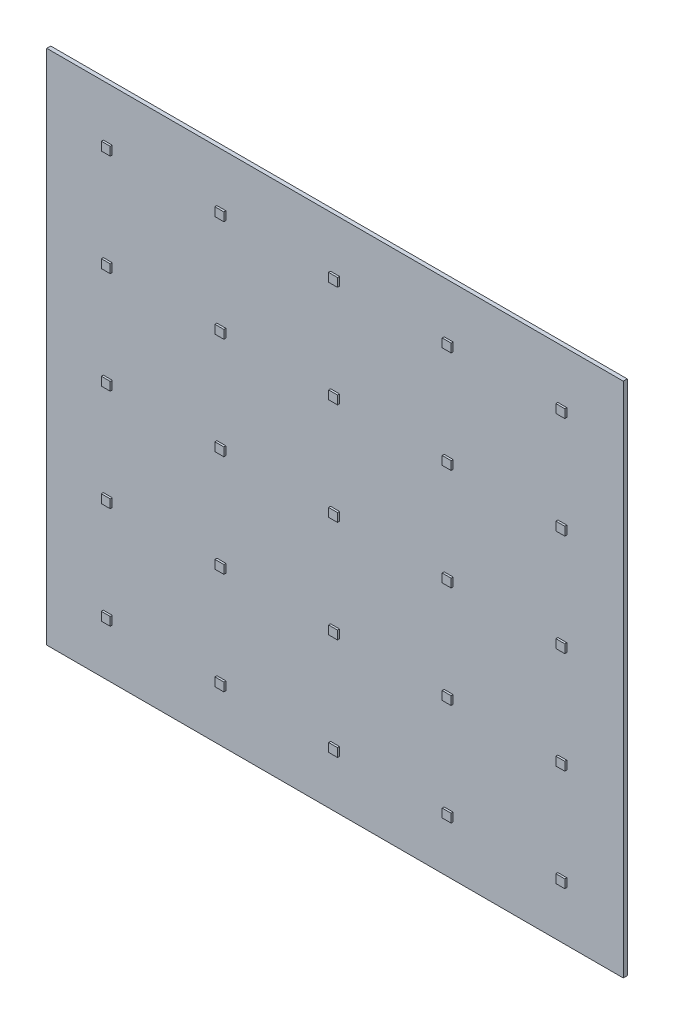
SolidWorks part; units mm, degrees
ref_plane "前视基准面" through (0, 0, 0) normal (0, 0, 1) x (1, 0, 0)
ref_plane "上视基准面" through (0, 0, 0) normal (0, 1, 0) x (1, 0, 0)
ref_plane "右视基准面" through (0, 0, 0) normal (1, 0, 0) x (0, 0, -1)
sketch "草图1" plane through (0, 0, 0) normal (0, 0, 1) x (1, 0, 0)
  line L1 (-72.5, -65) -> (72.5, -65)
  line L2 (-72.5, -65) -> (-72.5, 65)
  line L3 (-72.5, 65) -> (72.5, 65)
  line L4 (72.5, -65) -> (72.5, 65)
  line L5 (-72.5, -65) -> (72.5, 65) construction
  line L6 (-72.5, 65) -> (72.5, -65) construction
  point P0 (0, 0)
  dimension "D1" = 130
  dimension "D2" = 145
extrude "凸台-拉伸1" add sketch "草图1" along normal blind 1
sketch "草图2" plane through (0, 0, 1) normal (0, 0, 1) x (1, 0, 0)
  line L0 (-29.705, 49.9885) -> (-29.705, 52.1385)
  line L1 (-58.285, 49.9885) -> (-56.035, 49.9885)
  line L2 (-58.285, 49.9885) -> (-58.285, 52.1385)
  line L3 (-58.285, 52.1385) -> (-56.035, 52.1385)
  line L4 (-56.035, 49.9885) -> (-56.035, 52.1385)
  line L5 (-58.285, 49.9885) -> (-56.035, 52.1385) construction
  line L6 (-58.285, 52.1385) -> (-56.035, 49.9885) construction
  line L7 (-29.705, 49.9885) -> (-27.455, 49.9885)
  line L8 (-27.455, 49.9885) -> (-27.455, 52.1385)
  line L9 (-29.705, 52.1385) -> (-27.455, 52.1385)
  line L10 (-29.705, 49.9885) -> (-27.455, 52.1385) construction
  line L11 (-29.705, 52.1385) -> (-27.455, 49.9885) construction
  line L12 (-1.125, 49.9885) -> (-1.125, 52.1385)
  line L13 (-1.125, 49.9885) -> (1.125, 49.9885)
  line L14 (1.125, 49.9885) -> (1.125, 52.1385)
  line L15 (-1.125, 52.1385) -> (1.125, 52.1385)
  line L16 (-1.125, 49.9885) -> (1.125, 52.1385) construction
  line L17 (-1.125, 52.1385) -> (1.125, 49.9885) construction
  line L18 (27.455, 49.9885) -> (27.455, 52.1385)
  line L19 (27.455, 49.9885) -> (29.705, 49.9885)
  line L20 (29.705, 49.9885) -> (29.705, 52.1385)
  line L21 (27.455, 52.1385) -> (29.705, 52.1385)
  line L22 (27.455, 49.9885) -> (29.705, 52.1385) construction
  line L23 (27.455, 52.1385) -> (29.705, 49.9885) construction
  line L24 (56.035, 49.9885) -> (56.035, 52.1385)
  line L25 (56.035, 49.9885) -> (58.285, 49.9885)
  line L26 (58.285, 49.9885) -> (58.285, 52.1385)
  line L27 (56.035, 52.1385) -> (58.285, 52.1385)
  line L28 (56.035, 49.9885) -> (58.285, 52.1385) construction
  line L29 (56.035, 52.1385) -> (58.285, 49.9885) construction
  line L30 (-29.705, 24.3885) -> (-29.705, 26.5385)
  line L31 (-29.705, 24.3885) -> (-27.455, 24.3885)
  line L32 (-27.455, 24.3885) -> (-27.455, 26.5385)
  line L33 (-29.705, 26.5385) -> (-27.455, 26.5385)
  line L34 (-29.705, 24.3885) -> (-27.455, 26.5385) construction
  line L35 (-29.705, 26.5385) -> (-27.455, 24.3885) construction
  line L36 (-1.125, 24.3885) -> (-1.125, 26.5385)
  line L37 (-1.125, 24.3885) -> (1.125, 24.3885)
  line L38 (1.125, 24.3885) -> (1.125, 26.5385)
  line L39 (-1.125, 26.5385) -> (1.125, 26.5385)
  line L40 (-1.125, 24.3885) -> (1.125, 26.5385) construction
  line L41 (-1.125, 26.5385) -> (1.125, 24.3885) construction
  line L42 (27.455, 24.3885) -> (27.455, 26.5385)
  line L43 (27.455, 24.3885) -> (29.705, 24.3885)
  line L44 (29.705, 24.3885) -> (29.705, 26.5385)
  line L45 (27.455, 26.5385) -> (29.705, 26.5385)
  line L46 (27.455, 24.3885) -> (29.705, 26.5385) construction
  line L47 (27.455, 26.5385) -> (29.705, 24.3885) construction
  line L48 (56.035, 24.3885) -> (56.035, 26.5385)
  line L49 (56.035, 24.3885) -> (58.285, 24.3885)
  line L50 (58.285, 24.3885) -> (58.285, 26.5385)
  line L51 (56.035, 26.5385) -> (58.285, 26.5385)
  line L52 (56.035, 24.3885) -> (58.285, 26.5385) construction
  line L53 (56.035, 26.5385) -> (58.285, 24.3885) construction
  line L54 (-29.705, -1.2115) -> (-29.705, 0.9385)
  line L55 (-29.705, -1.2115) -> (-27.455, -1.2115)
  line L56 (-27.455, -1.2115) -> (-27.455, 0.9385)
  line L57 (-29.705, 0.9385) -> (-27.455, 0.9385)
  line L58 (-29.705, -1.2115) -> (-27.455, 0.9385) construction
  line L59 (-29.705, 0.9385) -> (-27.455, -1.2115) construction
  line L60 (-1.125, -1.2115) -> (-1.125, 0.9385)
  line L61 (-1.125, -1.2115) -> (1.125, -1.2115)
  line L62 (1.125, -1.2115) -> (1.125, 0.9385)
  line L63 (-1.125, 0.9385) -> (1.125, 0.9385)
  line L64 (-1.125, -1.2115) -> (1.125, 0.9385) construction
  line L65 (-1.125, 0.9385) -> (1.125, -1.2115) construction
  line L66 (27.455, -1.2115) -> (27.455, 0.9385)
  line L67 (27.455, -1.2115) -> (29.705, -1.2115)
  line L68 (29.705, -1.2115) -> (29.705, 0.9385)
  line L69 (27.455, 0.9385) -> (29.705, 0.9385)
  line L70 (27.455, -1.2115) -> (29.705, 0.9385) construction
  line L71 (27.455, 0.9385) -> (29.705, -1.2115) construction
  line L72 (56.035, -1.2115) -> (56.035, 0.9385)
  line L73 (56.035, -1.2115) -> (58.285, -1.2115)
  line L74 (58.285, -1.2115) -> (58.285, 0.9385)
  line L75 (56.035, 0.9385) -> (58.285, 0.9385)
  line L76 (56.035, -1.2115) -> (58.285, 0.9385) construction
  line L77 (56.035, 0.9385) -> (58.285, -1.2115) construction
  line L78 (-29.705, -26.8115) -> (-29.705, -24.6615)
  line L79 (-29.705, -26.8115) -> (-27.455, -26.8115)
  line L80 (-27.455, -26.8115) -> (-27.455, -24.6615)
  line L81 (-29.705, -24.6615) -> (-27.455, -24.6615)
  line L82 (-29.705, -26.8115) -> (-27.455, -24.6615) construction
  line L83 (-29.705, -24.6615) -> (-27.455, -26.8115) construction
  line L84 (-1.125, -26.8115) -> (-1.125, -24.6615)
  line L85 (-1.125, -26.8115) -> (1.125, -26.8115)
  line L86 (1.125, -26.8115) -> (1.125, -24.6615)
  line L87 (-1.125, -24.6615) -> (1.125, -24.6615)
  line L88 (-1.125, -26.8115) -> (1.125, -24.6615) construction
  line L89 (-1.125, -24.6615) -> (1.125, -26.8115) construction
  line L90 (27.455, -26.8115) -> (27.455, -24.6615)
  line L91 (27.455, -26.8115) -> (29.705, -26.8115)
  line L92 (29.705, -26.8115) -> (29.705, -24.6615)
  line L93 (27.455, -24.6615) -> (29.705, -24.6615)
  line L94 (27.455, -26.8115) -> (29.705, -24.6615) construction
  line L95 (27.455, -24.6615) -> (29.705, -26.8115) construction
  line L96 (56.035, -26.8115) -> (56.035, -24.6615)
  line L97 (56.035, -26.8115) -> (58.285, -26.8115)
  line L98 (58.285, -26.8115) -> (58.285, -24.6615)
  line L99 (56.035, -24.6615) -> (58.285, -24.6615)
  line L100 (56.035, -26.8115) -> (58.285, -24.6615) construction
  line L101 (56.035, -24.6615) -> (58.285, -26.8115) construction
  line L102 (-29.705, -52.4115) -> (-29.705, -50.2615)
  line L103 (-29.705, -52.4115) -> (-27.455, -52.4115)
  line L104 (-27.455, -52.4115) -> (-27.455, -50.2615)
  line L105 (-29.705, -50.2615) -> (-27.455, -50.2615)
  line L106 (-29.705, -52.4115) -> (-27.455, -50.2615) construction
  line L107 (-29.705, -50.2615) -> (-27.455, -52.4115) construction
  line L108 (-1.125, -52.4115) -> (-1.125, -50.2615)
  line L109 (-1.125, -52.4115) -> (1.125, -52.4115)
  line L110 (1.125, -52.4115) -> (1.125, -50.2615)
  line L111 (-1.125, -50.2615) -> (1.125, -50.2615)
  line L112 (-1.125, -52.4115) -> (1.125, -50.2615) construction
  line L113 (-1.125, -50.2615) -> (1.125, -52.4115) construction
  line L114 (27.455, -52.4115) -> (27.455, -50.2615)
  line L115 (27.455, -52.4115) -> (29.705, -52.4115)
  line L116 (29.705, -52.4115) -> (29.705, -50.2615)
  line L117 (27.455, -50.2615) -> (29.705, -50.2615)
  line L118 (27.455, -52.4115) -> (29.705, -50.2615) construction
  line L119 (27.455, -50.2615) -> (29.705, -52.4115) construction
  line L120 (56.035, -52.4115) -> (56.035, -50.2615)
  line L121 (56.035, -52.4115) -> (58.285, -52.4115)
  line L122 (58.285, -52.4115) -> (58.285, -50.2615)
  line L123 (56.035, -50.2615) -> (58.285, -50.2615)
  line L124 (56.035, -52.4115) -> (58.285, -50.2615) construction
  line L125 (56.035, -50.2615) -> (58.285, -52.4115) construction
  line L126 (-58.285, 24.3885) -> (-58.285, 26.5385)
  line L127 (-58.285, 24.3885) -> (-56.035, 24.3885)
  line L128 (-56.035, 24.3885) -> (-56.035, 26.5385)
  line L129 (-58.285, 26.5385) -> (-56.035, 26.5385)
  line L130 (-58.285, 24.3885) -> (-56.035, 26.5385) construction
  line L131 (-58.285, 26.5385) -> (-56.035, 24.3885) construction
  line L132 (-58.285, -1.2115) -> (-58.285, 0.9385)
  line L133 (-58.285, -1.2115) -> (-56.035, -1.2115)
  line L134 (-56.035, -1.2115) -> (-56.035, 0.9385)
  line L135 (-58.285, 0.9385) -> (-56.035, 0.9385)
  line L136 (-58.285, -1.2115) -> (-56.035, 0.9385) construction
  line L137 (-58.285, 0.9385) -> (-56.035, -1.2115) construction
  line L138 (-58.285, -26.8115) -> (-58.285, -24.6615)
  line L139 (-58.285, -26.8115) -> (-56.035, -26.8115)
  line L140 (-56.035, -26.8115) -> (-56.035, -24.6615)
  line L141 (-58.285, -24.6615) -> (-56.035, -24.6615)
  line L142 (-58.285, -26.8115) -> (-56.035, -24.6615) construction
  line L143 (-58.285, -24.6615) -> (-56.035, -26.8115) construction
  line L144 (-58.285, -52.4115) -> (-58.285, -50.2615)
  line L145 (-58.285, -52.4115) -> (-56.035, -52.4115)
  line L146 (-56.035, -52.4115) -> (-56.035, -50.2615)
  line L147 (-58.285, -50.2615) -> (-56.035, -50.2615)
  line L148 (-58.285, -52.4115) -> (-56.035, -50.2615) construction
  line L149 (-58.285, -50.2615) -> (-56.035, -52.4115) construction
  line L150 (0, -65) -> (0, 65) construction
  line L151 (-72.5, -65) -> (72.5, -65) construction
  line L152 (72.5, 65) -> (-72.5, 65) construction
  point P0 (-57.16, 51.0635)
  point P8 (-28.58, 51.0635)
  point P13 (0, 51.0635)
  point P18 (28.58, 51.0635)
  point P23 (57.16, 51.0635)
  point P28 (-28.58, 25.4635)
  point P33 (0, 25.4635)
  point P38 (28.58, 25.4635)
  point P43 (57.16, 25.4635)
  point P48 (-28.58, -0.1365)
  point P53 (0, -0.1365)
  point P58 (28.58, -0.1365)
  point P63 (57.16, -0.1365)
  point P68 (-28.58, -25.7365)
  point P73 (0, -25.7365)
  point P78 (28.58, -25.7365)
  point P83 (57.16, -25.7365)
  point P88 (-28.58, -51.3365)
  point P93 (0, -51.3365)
  point P98 (28.58, -51.3365)
  point P103 (57.16, -51.3365)
  point P108 (-57.16, 25.4635)
  point P113 (-57.16, -0.1365)
  point P118 (-57.16, -25.7365)
  point P123 (-57.16, -51.3365)
  point P131 (0, 0)
  dimension "D1" = 2.15
  dimension "D2" = 2.25
  dimension "D3" = 5
  dimension "D4" = 5
extrude "凸台-拉伸2" add sketch "草图2" along normal blind 0.5
